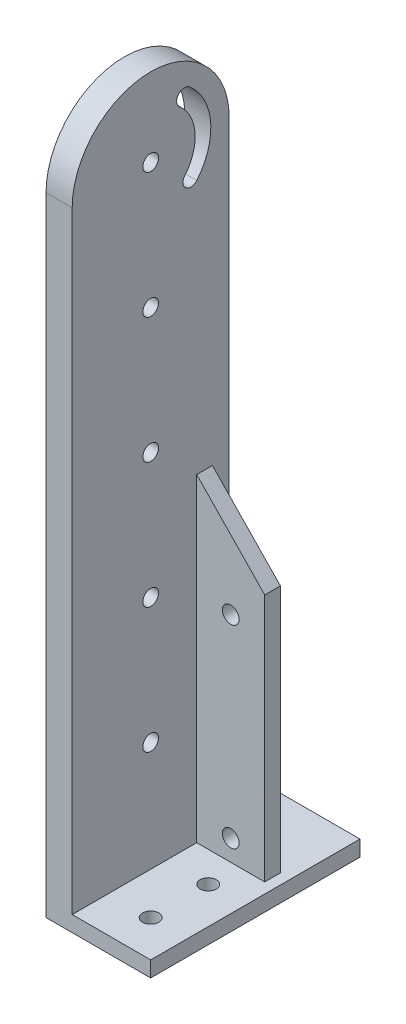
SolidWorks part; units mm, degrees
ref_plane "前视基准面" through (0, 0, 0) normal (0, 0, 1) x (1, 0, 0)
ref_plane "上视基准面" through (0, 0, 0) normal (0, 1, 0) x (1, 0, 0)
ref_plane "右视基准面" through (0, 0, 0) normal (1, 0, 0) x (0, 0, -1)
sketch "草图1" plane through (0, 0, 0) normal (1, 0, 0) x (0, 0, -1)
  line L0 (-15, 0) -> (15, 0)
  line L1 (-15, 0) -> (-15, 120)
  line L2 (15, 0) -> (15, 120)
  line L10 (0, 120) -> (-7.6604, 113.5721) construction
  line L12 (0, 120) -> (-10, 120) construction
  line L13 (-6.4279, 127.6604) -> (0, 120) construction
  circle A2 centre (0, 24) radius 1.5
  circle A3 centre (0, 48) radius 1.5
  circle A4 centre (0, 72) radius 1.5
  circle A5 centre (0, 96) radius 1.5
  circle A9 centre (0, 120) radius 1.5
  circle A11 centre (0, 120) radius 10 construction
  arc A13 (-8.8095, 112.6079) -> (-6.5114, 114.5363) centre (-7.6604, 113.5721) ccw construction
  arc A14 (-8.8095, 112.6079) -> (-7.3921, 128.8095) centre (0, 120) cw construction
  arc A15 (-5.4637, 126.5114) -> (-7.3921, 128.8095) centre (-6.4279, 127.6604) ccw construction
  arc A16 (-6.5114, 114.5363) -> (-5.4637, 126.5114) centre (0, 120) cw construction
  arc A21 (15, 120) -> (-15, 120) centre (0, 120) ccw
  arc A24 (5.4914, 126.488) -> (7.4295, 128.7779) centre (6.4605, 127.633) cw
  arc A26 (6.5114, 114.5363) -> (5.4914, 126.488) centre (0, 120) ccw
  arc A27 (8.8095, 112.6079) -> (7.4295, 128.7779) centre (0, 120) ccw
  arc A28 (8.8095, 112.6079) -> (6.5114, 114.5363) centre (7.6604, 113.5721) cw
  point P3 (0, 0)
  dimension "D5" = 1.5
  dimension "D4" = 3
  dimension "D9" = 40
  dimension "D11" = 1.5
  dimension "D16" = 50
  dimension "D12" = 1.5
  dimension "D3" = 1.5
  dimension "D1" = 30
  dimension "D2" = 120
  dimension "D6" = 24
  dimension "D10" = 15
  dimension "D13" = 24
  dimension "D14" = 24
  dimension "D15" = 24
  dimension "D17" = 10
extrude "凸台-拉伸2" add sketch "草图1" against normal blind 5
ref_plane "基准面1" through (-5, 0, 0) normal (-1, 0, 0) x (0, 0, 1)
ref_plane "基准面3" through (-30, 0, 0) normal (-1, 0, 0) x (0, 0, 1)
ref_plane "基准面4" through (0, 0, 0) normal (0, -1, 0) x (-1, 0, 0)
sketch "草图4" plane through (0, 0, 0) normal (0, -1, 0) x (-1, 0, 0)
  line L0 (5, -15) -> (-15, -15)
  line L1 (5, -15) -> (0, -15) construction
  line L2 (-15, -15) -> (-15, 25)
  line L3 (-15, 25) -> (8, 25)
  line L4 (5, 15) -> (5, -15)
  line L5 (5, -15) -> (5, 15) construction
  line L9 (8, 25) -> (8, 15)
  line L10 (8, 15) -> (5, 15)
  dimension "D2" = 40
  dimension "D3" = 3
  dimension "D4" = 10
  dimension "D5" = 20
extrude "凸台-拉伸3" add sketch "草图4" against normal blind 3
sketch "草图5" plane through (0, 0, 0) normal (0, -1, 0) x (1, 0, 0)
  line L0 (-8, -15) -> (-8, -25) construction
  line L1 (-5, -15) -> (-8, -15) construction
  line L3 (-5, 15) -> (15, 15) construction
  circle A1 centre (8, 8) radius 1.55
  circle A2 centre (-3, -20) radius 1.55
  circle A3 centre (8, -3) radius 1.55
  dimension "D1" = 5
  dimension "D4" = 3.1
  dimension "D3" = 3.1
  dimension "D6" = 11
  dimension "D7" = 3.1
  dimension "D2" = 5
  dimension "D5" = 7
extrude "切除-拉伸3" cut sketch "草图5" against normal blind 10
sketch "草图6" plane through (0, 0, 0) normal (1, 0, 0) x (0, 0, -1)
  line L0 (15, 3) -> (-15, 3) construction
  line L1 (8.8, 3) -> (11.8, 3)
  line L2 (8.8, 3) -> (8.8, 44)
  line L3 (8.8, 44) -> (11.8, 44)
  line L4 (11.8, 3) -> (11.8, 44)
  line L5 (15, 3) -> (15, 120) construction
  dimension "D1" = 3
  dimension "D2" = 3.2
  dimension "D3" = 41
extrude "凸台-拉伸4" add sketch "草图6" along normal blind 13
sketch "草图8" plane through (0, 0, -11.8) normal (0, 0, -1) x (-1, 0, 0)
  line L0 (-13, 50.5) -> (0, 63.9333)
  line L1 (-13, 44) -> (0, 44)
  line L2 (-13, 50.5) -> (0, 50.5) construction
  line L3 (0, 3) -> (0, 120) construction
  line L4 (0, 50.5) -> (0, 44)
  line L5 (-13, 50.5) -> (-13, 44)
  line L6 (0, 63.9333) -> (0, 50.5)
extrude "凸台-拉伸5" add sketch "草图8" against normal blind 3
sketch "草图9" plane through (0, 0, -11.8) normal (0, 0, -1) x (-1, 0, 0)
  line L1 (0, 3) -> (0, 120) construction
  line L2 (-13, 50.5) -> (0, 50.5) construction
  line L3 (0, 3) -> (0, 63.9333) construction
  circle A0 centre (-6.5, 44) radius 1.6
  circle A1 centre (-6.5, 7) radius 1.6
  dimension "D1" = 37
  dimension "D2" = 6.5
  dimension "D3" = 6.5
extrude "切除-拉伸4" cut sketch "草图9" against normal blind 3
sketch "草图13" plane through (-5, 0, 0) normal (-1, 0, 0) x (0, 0, 1)
  line L0 (-10, 24) -> (-10, 96)
  line L1 (10, 24) -> (10, 96)
  line L6 (4.7432, 121.5817) -> (4.7194, 121.6515)
  arc A0 (4.7432, 121.5817) -> (4.7194, 121.6515) centre (0, 120) ccw
  arc A1 (-10, 24) -> (10, 24) centre (0, 24) ccw
  arc A2 (10, 96) -> (-10, 96) centre (0, 96) ccw
  circle M11 centre (0, 120) radius 1.5
  circle M12 centre (0, 96) radius 1.5
  circle M13 centre (0, 72) radius 1.5
  circle M18 centre (0, 48) radius 1.5
  circle M19 centre (0, 24) radius 1.5
  dimension "D1" = 20
  dimension "D2" = 10
extrude "切除-拉伸6" cut sketch "草图13" against normal blind 1 contours L0 A1 L1 L6 A0 M12 M18 M19 M13 M11 region at (-5, 60, 0)
